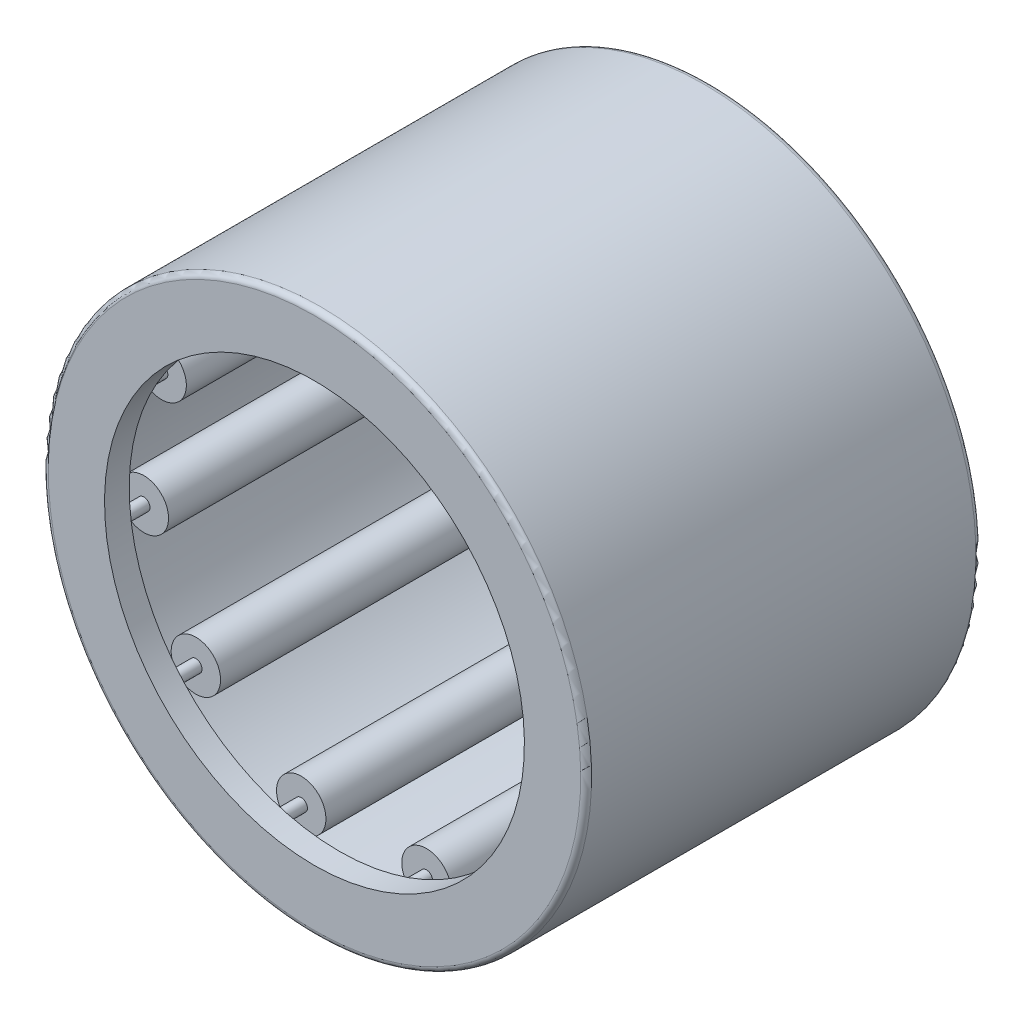
SolidWorks part; units mm, degrees
note: '?' marks a value the reader was unsure of.
ref_plane "Front Plane" through (0, 0, 0) normal (0, 0, 1) x (1, 0, 0)
ref_plane "Top Plane" through (0, 0, 0) normal (0, 1, 0) x (1, 0, 0)
ref_plane "Right Plane" through (0, 0, 0) normal (1, 0, 0) x (0, 0, -1)
sketch "Sketch1" plane through (0, 0, 0) normal (1, 0, 0) x (0, 0, -1)
  line L0 (-6.35, 0) -> (6.35, 0) construction
  line L1 (0, 0) -> (0, 8.7312) construction
  line L2 (-6.35, 0) -> (-6.35, 8.7312) construction
  line L3 (-6.35, 8.7312) -> (6.35, 8.7312)
  line L4 (6.35, 8.7312) -> (6.35, 0) construction
  line L5 (6.35, 0) -> (5.5562, 0) construction
  line L6 (5.5562, 0) -> (5.5563, 7.9375) construction
  line L7 (5.5563, 7.9375) -> (-5.5563, 7.9375)
  line L8 (-5.5563, 7.9375) -> (-5.5562, 0) construction
  line L9 (-5.5562, 0) -> (-6.35, 0) construction
  line L10 (-6.35, 8.7312) -> (-6.35, 6.7469)
  line L11 (-6.35, 6.7469) -> (-5.5562, 6.7469)
  line L12 (-5.5562, 6.7469) -> (-5.5563, 7.9375)
  line L13 (5.5563, 8.7313) -> (5.5563, 7.9375) construction
  line L14 (5.5563, 7.9375) -> (5.5562, 6.7469)
  line L15 (5.5562, 6.7469) -> (6.35, 6.7469)
  line L16 (6.35, 6.7469) -> (6.35, 8.7312)
  line L17 (5.5563, 7.9375) -> (5.5563, 7.1438) construction
  line L18 (5.5563, 7.1438) -> (5.5563, 6.35) construction
  point P5 (0, 6.35)
  dimension "Width" = 12.7
  dimension "OD" = 17.4625
  dimension "Shaft Dia" = 12.7
revolve "Revolve1" add sketch "Sketch1" angle 360 about L0
sketch "Sketch2" plane through (0, 0, 0) normal (1, 0, 0) x (0, 0, -1)
  line L0 (5.5563, 7.9375) -> (-5.5563, 7.9375) construction
  line L1 (-4.7625, 7.1438) -> (4.7625, 7.1438) construction
  line L2 (-4.7625, 7.1438) -> (-4.7625, 7.9375) construction
  line L3 (-4.7625, 7.9375) -> (4.7625, 7.9375)
  line L4 (4.7625, 7.1438) -> (4.7625, 7.9375) construction
  line L5 (5.5562, 6.7469) -> (6.35, 6.7469) construction
  line L6 (-5.5562, 7.1437) -> (-4.7625, 7.1438) construction
  line L7 (4.7625, 7.1438) -> (5.5562, 7.1438) construction
  line L8 (-6.35, 6.7469) -> (-5.5562, 6.7469) construction
  line L9 (-4.7625, 7.3422) -> (-4.7625, 6.9453) construction
  line L10 (-5.5562, 7.1437) -> (-5.5562, 6.7469) construction
  line L11 (-4.7625, 7.9375) -> (-4.7625, 7.3422)
  line L12 (4.7625, 7.9375) -> (4.7625, 7.3422)
  line L13 (4.7625, 7.3422) -> (-4.7625, 7.3422)
  line L14 (0, 7.9375) -> (0, 6.35) construction
  line L15 (-5.5562, 6.7469) -> (-5.5562, 7.9375) construction
  line L16 (-4.7625, 6.9453) -> (-5.5563, 6.9453) construction
  line L17 (0, 0) -> (6.35, 0) construction
  line L31 (6.35, -8.7313) -> (6.35, 8.7312) construction
  point P16 (0, 7.1437)
revolve "Revolve2" add sketch "Sketch2" angle 360 about L1
sketch "Sketch3" plane through (0, 0, 0) normal (1, 0, 0) x (0, 0, -1)
  line L0 (5.5563, 7.9375) -> (5.5563, 6.7469) construction
  line L1 (-5.5562, 7.1437) -> (5.5563, 7.1437)
  line L2 (-5.5562, 7.1437) -> (-5.5562, 7.3422)
  line L3 (-5.5562, 7.3422) -> (5.5563, 7.3422)
  line L4 (5.5563, 7.1437) -> (5.5563, 7.3422)
  line L5 (0, 0) -> (6.35, 0) construction
  line L6 (6.35, -8.7313) -> (6.35, 8.7312) construction
revolve "Revolve3" add sketch "Sketch3" angle 360 about L1
ref_axis "Axis1" through (0, 0, -6.35) along (0, 0, 1)
pattern_circular "CirPattern1" count 11 every 32.727 about axis through (0, 0, -6.35) along (0, 0, 1) of bodies 166 167
fillet "Fillet1" radius 0.1746 2 edges at (0, -8.7313, -6.35) (0, -8.7312, 6.35)
sketch "Sketch4" plane through (0, 0, 0) normal (1, 0, 0) x (0, 0, -1)
  line L1 (6.1754, 6.35) -> (4.7625, 6.35)
  line L2 (6.1754, 6.35) -> (6.1754, 6.7469)
  line L3 (6.1754, 6.7469) -> (4.7625, 6.7469)
  line L4 (4.7625, 6.35) -> (4.7625, 6.7469)
  line L5 (-6.35, 6.7469) -> (-5.5562, 6.7469) construction
  line L6 (6.1754, -8.7313) -> (6.1754, 8.7312) construction
  line L7 (4.7625, 7.9375) -> (4.7625, 7.3422) construction
revolve "Revolve4" [suppressed] add sketch "Sketch4" angle 360 about L0
sketch "Sketch5" plane through (0, 0, 0) normal (1, 0, 0) x (0, 0, -1)
  line L0 (-6.1754, 8.7312) -> (-6.1754, -8.7312) construction
  line L1 (-4.7625, 6.35) -> (-6.1754, 6.35)
  line L2 (-4.7625, 6.35) -> (-4.7625, 6.7469)
  line L3 (-4.7625, 6.7469) -> (-6.1754, 6.7469)
  line L4 (-6.1754, 6.35) -> (-6.1754, 6.7469)
  line L6 (-4.7625, 7.9375) -> (-4.7625, 7.3422) construction
  line L7 (-6.35, 6.7469) -> (-5.5562, 6.7469) construction
revolve "Revolve5" [suppressed] add sketch "Sketch5" angle 360 about L0
sketch "Front View" plane through (0, 0, 0) normal (0, 0, 1) x (1, 0, 0)
  circle A0 centre (0, 0) radius 6.35 construction
  circle A1 centre (0, 0) radius 8.7312 construction
  dimension "OD" = 17.4625
  dimension "ID" = 12.7
sketch "Right View" plane through (0, 0, 0) normal (1, 0, 0) x (0, 0, -1)
  line L0 (-6.35, 8.7312) -> (6.35, 8.7312) construction
  dimension "Width" = 12.7
ref_axis "Center Axis 1" through (0, 0, -6.1754) along (0, 0, 1)?
ref_plane "Contact Plane 1" through (0, 0, 6.35) normal (0, 0, 1) x (1, 0, 0)
ref_plane "Contact Plane 2" through (0, 0, -6.35) normal (0, 0, -1) x (-1, 0, 0)
equation "\"Rollers@CirPattern1\" = \"OD@Sketch1\"*16"
equation "\"D1@Fillet1\" = \"OD@Sketch1\"*.01"
equation "\"Angle@CirPattern1\"= 360 / \"Rollers@CirPattern1\""
equation "\"OD@Front View\"=\"OD@Sketch1\""
equation "\"ID@Front View\"=\"Shaft Dia@Sketch1\""
equation "\"Width@Right View\"=\"Width@Sketch1\""
